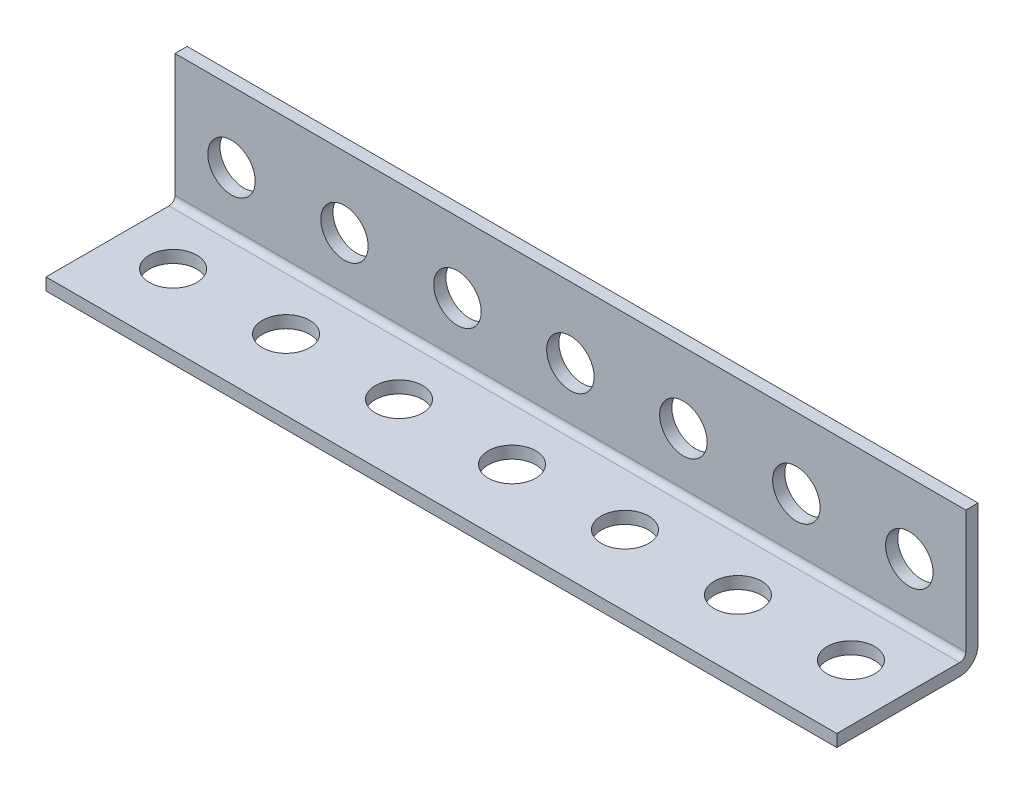
SolidWorks part; units mm, degrees
material "Galvanized Steel"
ref_plane "Front Plane" through (0, 0, 0) normal (0, 0, 1) x (1, 0, 0)
ref_plane "Top Plane" through (0, 0, 0) normal (0, 1, 0) x (1, 0, 0)
ref_plane "Right Plane" through (0, 0, 0) normal (1, 0, 0) x (0, 0, -1)
sketch "Sketch1" plane through (0, 0, 0) normal (1, 0, 0) x (0, 0, -1)
  line L0 (-15.875, -13.1318) -> (13.1318, -13.1318) construction
  line L1 (13.1318, -13.1318) -> (13.1318, 15.875) construction
  line L2 (13.1318, 15.875) -> (15.875, 15.875) construction
  line L3 (15.875, 15.875) -> (15.875, -15.875) construction
  line L4 (15.875, -15.875) -> (-15.875, -15.875) construction
  line L5 (-15.875, -15.875) -> (-15.875, -13.1318) construction
  line L6 (0, -15.875) -> (0, 15.875) construction
  line L7 (15.875, 0) -> (-15.875, 0) construction
  dimension "Thickness | T" = 2.7432
  dimension "Width (A)" = 31.75
  dimension "Width (B)" = 31.75
sketch "Sketch2" plane through (0, 0, 0) normal (0, 0, 1) x (1, 0, 0)
  line L0 (-609.6, 0) -> (609.6, 0) construction
  line L1 (-609.6, 15.875) -> (609.6, 15.875) construction
  line L2 (-609.6, 15.875) -> (-609.6, -15.875) construction
  line L3 (-609.6, -15.875) -> (609.6, -15.875) construction
  line L4 (609.6, 15.875) -> (609.6, -15.875) construction
  line L5 (0, 15.875) -> (0, -15.875) construction
  line L7 (-609.6, -13.1318) -> (609.6, -13.1318) construction
  circle A0 centre (596.9, 0) radius 5.334 construction
  circle A1 centre (571.5, 0) radius 5.334 construction
  point P15 (533.4, 0)
  point P16 (-533.4, 0)
  point P24 (602.234, 0)
  dimension "Mounting Hole Diameter" = 10.668
  dimension "Length | L" = 1219.2
  dimension "Mounting Hole Center to Center" = 25.4
  dimension "D1" = 12.7
  dimension "D2" = 63.5
sketch "Sketch3" plane through (0, 0, 0) normal (0, 1, 0) x (1, 0, 0)
  line L1 (-609.6, 15.875) -> (609.6, 15.875) construction
  line L2 (-609.6, 15.875) -> (-609.6, -15.875) construction
  line L3 (-609.6, -15.875) -> (609.6, -15.875) construction
  line L4 (609.6, 15.875) -> (609.6, -15.875) construction
  line L5 (-609.6, 13.1318) -> (609.6, 13.1318) construction
  line L7 (-609.6, 0) -> (609.6, 0) construction
  circle A0 centre (596.9, 0) radius 5.334 construction
  circle A1 centre (571.5, 0) radius 5.334 construction
  point P19 (-533.4, 0)
  point P21 (602.234, 0)
  point P22 (533.4, 0)
sketch "Sketch4" plane through (0, 0, 0) normal (1, 0, 0) x (0, 0, -1)
  line L0 (-15.875, -13.1318) -> (11.7602, -13.1318)
  line L1 (13.1318, -11.7602) -> (13.1318, 15.875)
  line L2 (13.1318, 15.875) -> (15.875, 15.875)
  line L3 (15.875, 15.875) -> (15.875, -11.7602)
  line L4 (11.7602, -15.875) -> (-15.875, -15.875)
  line L5 (-15.875, -15.875) -> (-15.875, -13.1318)
  line L6 (11.7602, -13.1318) -> (11.7602, -10.3886) construction
  arc A0 (11.7602, -13.1318) -> (13.1318, -11.7602) centre (11.7602, -11.7602) ccw
  arc A1 (15.875, -11.7602) -> (11.7602, -15.875) centre (11.7602, -11.7602) cw
extrude "Boss-Extrude1" add sketch "Sketch4" along normal up to vertex (609.6 mm away) and the other way up to vertex (609.6 mm away) up to point (609.6, 0, 0) other way up to point (-609.6, 0, 0)
sketch "Sketch5" plane through (0, 0, 0) normal (0, 0, 1) x (1, 0, 0)
  circle A0 centre (596.9, 0) radius 5.334
extrude "Cut-Extrude1" cut sketch "Sketch5" against normal through all
sketch "Sketch6" plane through (0, 0, 0) normal (0, 1, 0) x (1, 0, 0)
  circle A0 centre (596.9, 0) radius 5.334
extrude "Cut-Extrude2" cut sketch "Sketch6" against normal through all
pattern_linear "LPattern1" count 48 spacing 25.4 along (-1, 0, 0) of "Cut-Extrude2", "Cut-Extrude1"
sketch "Sketch7" plane through (0, 0, -15.875) normal (0, 0, -1) x (-1, 0, 0)
  line L0 (-609.6, -15.875) -> (609.6, -15.875) construction
  line L1 (-609.6, 15.875) -> (25.4, 15.875)
  line L2 (-609.6, 15.875) -> (-609.6, -15.875)
  line L3 (-609.6, -15.875) -> (25.4, -15.875)
  line L4 (25.4, 15.875) -> (25.4, -15.875)
  line L5 (602.234, 0) -> (609.6, 0) construction
  line L6 (609.6, -11.7602) -> (609.6, 15.875) construction
  line L7 (32.766, 0) -> (25.4, 0)
  circle A0 centre (596.9, 0) radius 5.334 construction
  circle A1 centre (38.1, 0) radius 5.334 construction
  dimension "D1" = 7.366
extrude "Cut-Extrude3" cut sketch "Sketch7" against normal blind 70 contours L4 L1 L2 L3 region at (292.1, 0, -15.875)
sketch "Sketch8" plane through (0, 0, -15.875) normal (0, 0, -1) x (-1, 0, 0)
  line L0 (25.4, -15.875) -> (609.6, -15.875) construction
  line L1 (25.4, 15.875) -> (50.8, 15.875)
  line L2 (25.4, 15.875) -> (25.4, -15.875)
  line L3 (25.4, -15.875) -> (50.8, -15.875)
  line L4 (50.8, 15.875) -> (50.8, -15.875)
  line L6 (58.166, 0) -> (50.8, 0)
  circle A0 centre (63.5, 0) radius 5.334 construction
  circle M28 centre (38.1, 0) radius 5.334
  line M29 (25.4, 15.875) -> (25.4, -11.7602)
  line M30 (25.4, -11.7602) -> (609.6, -11.7602)
  line M32 (609.6, 15.875) -> (25.4, 15.875)
  dimension "D1" = 7.366
extrude "Cut-Extrude4" cut sketch "Sketch8" against normal blind 70 contours L4 M32 M29 M30 M28 | L4 L2 L3 M30 region at (-38.1, 15.4997, -15.875) region at (-38.1, -13.8176, -15.875)
sketch "Sketch9" plane through (0, 0, -15.875) normal (0, 0, -1) x (-1, 0, 0)
  line L0 (50.8, -15.875) -> (609.6, -15.875) construction
  line L1 (50.8, 15.875) -> (431.8, 15.875)
  line L2 (50.8, 15.875) -> (50.8, -15.875)
  line L3 (50.8, -15.875) -> (431.8, -15.875)
  line L4 (431.8, 15.875) -> (431.8, -15.875)
  line L5 (439.166, 0) -> (431.8, 0)
  circle A0 centre (444.5, 0) radius 5.334 construction
  circle M7 centre (63.5, 0) radius 5.334
  circle M8 centre (88.9, 0) radius 5.334
  circle M9 centre (114.3, 0) radius 5.334
  circle M10 centre (139.7, 0) radius 5.334
  circle M11 centre (165.1, 0) radius 5.334
  circle M12 centre (190.5, 0) radius 5.334
  circle M13 centre (215.9, 0) radius 5.334
  circle M14 centre (241.3, 0) radius 5.334
  circle M15 centre (266.7, 0) radius 5.334
  circle M16 centre (292.1, 0) radius 5.334
  circle M17 centre (317.5, 0) radius 5.334
  circle M18 centre (342.9, 0) radius 5.334
  circle M19 centre (368.3, 0) radius 5.334
  circle M20 centre (393.7, 0) radius 5.334
  circle M21 centre (419.1, 0) radius 5.334
  line M29 (50.8, 15.875) -> (50.8, -11.7602)
  line M30 (50.8, -11.7602) -> (609.6, -11.7602)
  line M32 (609.6, 15.875) -> (50.8, 15.875)
  dimension "7.366" = 7.366
extrude "Cut-Extrude5" cut sketch "Sketch9" against normal blind 70 contours L4 M32 M29 M30 M8 M10 M12 M14 M16 M18 M20 M21 M19 M17 M15 M13 M11 M9 M7 | L4 L2 L3 M30 region at (-241.3, 12.055, -15.875) region at (-241.3, -13.8176, -15.875)
sketch "Sketch10" plane through (0, 0, -15.875) normal (0, 0, -1) x (-1, 0, 0)
  line L0 (439.166, 0) -> (431.8, 0)
  line L1 (431.8, 15.875) -> (431.8, -11.7602) construction
  line L2 (444.5, 5.334) -> (444.5, 15.875)
  line L3 (431.8, 15.875) -> (609.6, 15.875) construction
  line L4 (602.234, 0) -> (609.6, 0)
  line L5 (609.6, -11.7602) -> (609.6, 15.875) construction
  line L6 (596.9, 5.334) -> (596.9, 15.875)
  circle A0 centre (444.5, 0) radius 5.334 construction
  circle A1 centre (596.9, 0) radius 5.334 construction
sketch "Sketch11" plane through (0, -15.875, 0) normal (0, -1, 0) x (1, 0, 0)
  line L0 (-602.234, 0) -> (-609.6, 0)
  line L1 (-609.6, 15.875) -> (-609.6, -11.7602) construction
  line L2 (-596.9, 5.334) -> (-596.9, 15.875)
  line L3 (-431.8, 15.875) -> (-609.6, 15.875) construction
  line L4 (-439.166, 0) -> (-431.8, 0)
  line L5 (-431.8, 15.875) -> (-431.8, -11.7602) construction
  line L6 (-444.5, 5.334) -> (-444.5, 15.875)
  circle A0 centre (-596.9, 0) radius 5.334 construction
  circle A1 centre (-444.5, 0) radius 5.334 construction
equation "\"D1@Sketch2\"= ( \"Length | L@Sketch2\" - \"Mounting Hole Center to Center@Sketch2\" * \"Num Holes\" ) / 2"
equation "\"Num Holes\"= int ( \"Length | L@Sketch2\" / \"Mounting Hole Center to Center@Sketch2\" ) - 1"
equation "\"D2@Sketch2\"=\"Mounting Hole Center to Center@Sketch2\"*2.5"
equation "\"D3@LPattern1\"=\"Mounting Hole Center to Center@Sketch2\""
